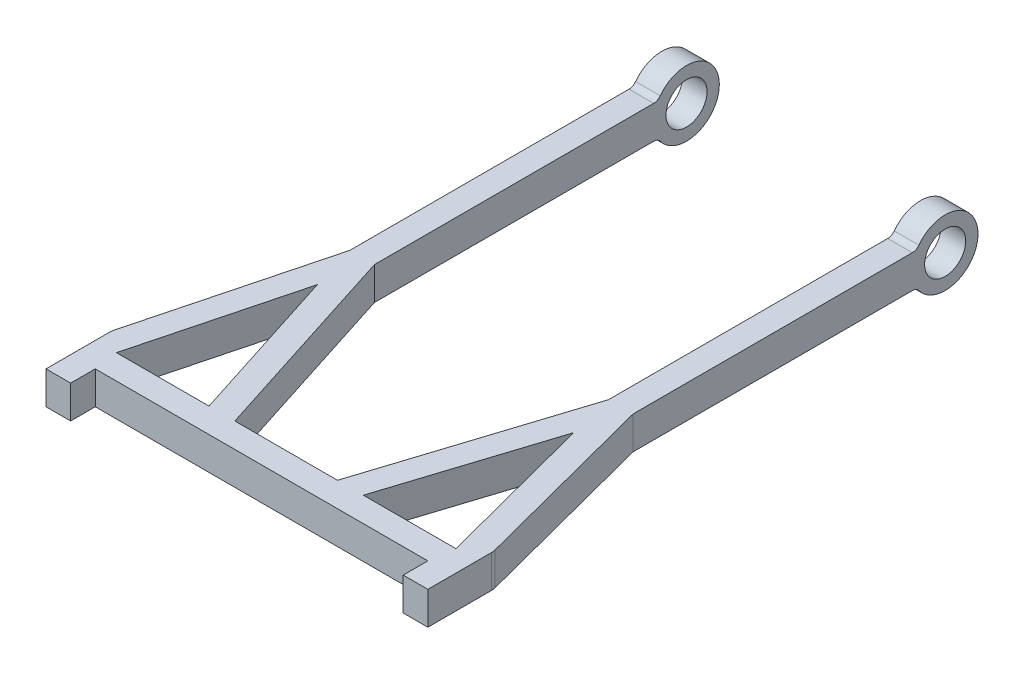
SolidWorks part; units mm, degrees
ref_plane "Front Plane" through (0, 0, 0) normal (0, 0, 1) x (1, 0, 0)
ref_plane "Top Plane" through (0, 0, 0) normal (0, 1, 0) x (1, 0, 0)
ref_plane "Right Plane" through (0, 0, 0) normal (1, 0, 0) x (0, 0, -1)
sketch "Sketch1" plane through (0, 0, 0) normal (0, 1, 0) x (1, 0, 0)
  line L6 (-4.6999, 0.75) -> (-7.8046, 10.4522)
  line L7 (-10.3357, 0.75) -> (-4.6999, 0.75)
  line L9 (-10.125, -0.75) -> (0, -0.75)
  line L10 (0, 0.75) -> (0, -0.75)
  line L11 (-3.125, 0.75) -> (-7.125, 13.25)
  line L12 (-7.8046, 10.4522) -> (-10.3357, 0.75)
  line L13 (-11.625, -0.75) -> (-11.625, 1.6217)
  line L14 (-11.5926, 1.8741) -> (-8.625, 13.25)
  line L15 (-3.125, 0.75) -> (0, 0.75)
  line L16 (0, 0.75) -> (0, 5.5445) construction
  line L17 (-8.625, 30.25) -> (-7.125, 30.25)
  line L18 (-8.625, 30.25) -> (-8.625, 13.25)
  line L19 (-8.625, 13.25) -> (-7.125, 13.25) construction
  line L20 (-7.125, 30.25) -> (-7.125, 13.25)
  line L21 (-11.625, -0.75) -> (-10.125, -0.75) construction
  line L22 (-11.625, -2.25) -> (-10.125, -2.25)
  line L23 (-11.625, -2.25) -> (-11.625, -0.75)
  line L25 (-10.125, -2.25) -> (-10.125, -0.75)
  arc A0 (-11.625, 1.6217) -> (-11.5926, 1.8741) centre (-10.625, 1.6217) cw
  point P20 (-11.625, 1.75)
  dimension "D13" = 1
  dimension "D1" = 1.5
  dimension "D2" = 1.5
  dimension "D3" = 1.5
  dimension "D4" = 1.5
  dimension "D5" = 6.25
  dimension "D6" = 14.25
  dimension "D7" = 23.25
  dimension "D8" = 2.5
  dimension "D9" = 14
  dimension "D10" = 31
  dimension "D11" = 1.5
  dimension "D12" = 1.5
extrude "Boss-Extrude1" add sketch "Sketch1" along normal mid plane 2
mirror "Mirror1" about plane through (0, 0, 0) normal (1, 0, 0) of "Boss-Extrude1"
sketch "Sketch2" plane through (0, 0, 0) normal (1, 0, 0) x (0, 0, -1)
  line L0 (30.25, 1) -> (30.25, -1)
  line L1 (0, 0) -> (10.9707, 0) construction
  line L2 (30.25, 1) -> (30.25, -1) construction
  arc A0 (30.65, -1.2) -> (30.65, 1.2) centre (32.25, 0) ccw
  arc A1 (30.25, 1) -> (30.65, 1.2) centre (30.25, 1.5) ccw
  arc A2 (30.25, -1) -> (30.65, -1.2) centre (30.25, -1.5) cw
  arc A3 (30.65, 1.2) -> (30.65, -1.2) centre (32.25, 0) ccw construction
  point P7 (30.25, 0)
  dimension "D1" = 4
  dimension "D2" = 0.5
extrude "Boss-Extrude2" add sketch "Sketch2" along normal up to surface (8.625 mm away) from surface up to face at (8.625, 0, -21.75) starting at face at (7.125, 0, -21.75)
extrude "Boss-Extrude3" add sketch "Sketch2<2>" along normal up to surface (-7.125 mm away) from surface up to face at (-7.125, 0, -21.75) starting at face at (-8.625, 0, -21.75)
sketch "Sketch2<2>" plane through (0, 0, 0) normal (1, 0, 0) x (0, 0, -1) same geometry as "Sketch2"
sketch "Sketch3" plane through (0, 0, 0) normal (1, 0, 0) x (0, 0, -1)
  circle A0 centre (32.25, 0) radius 1.25
  arc A1 (30.65, -1.2) -> (30.65, 1.2) centre (32.25, 0) ccw construction
  dimension "D1" = 2.5
extrude "Cut-Extrude1" cut sketch "Sketch3" against normal through all both and the other way through all
equation "\"univ\"= 6.25"
equation "\"D5@Sketch1\"=\"univ\""
equation "\"D6@Sketch1\"=\"univ\"+8"
equation "\"D7@Sketch1\"=\"univ\"+17"
